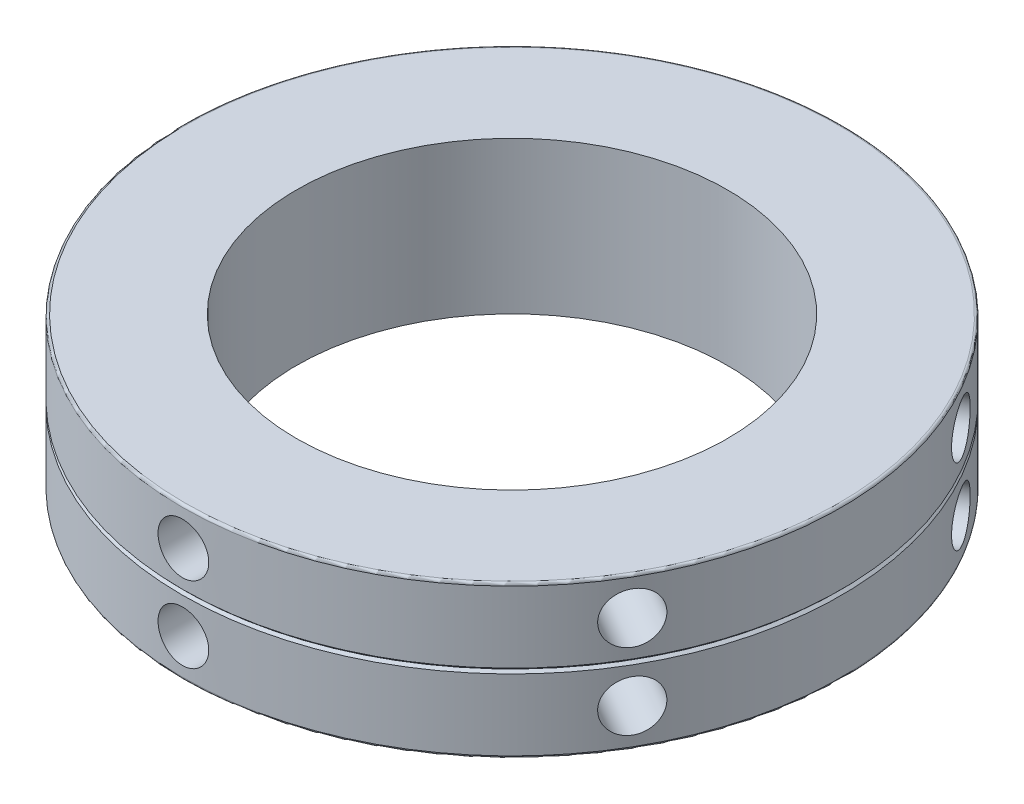
SolidWorks part; units mm, degrees
ref_plane "Front Plane" through (0, 0, 0) normal (0, 0, 1) x (1, 0, 0)
ref_plane "Top Plane" through (0, 0, 0) normal (0, 1, 0) x (1, 0, 0)
ref_plane "Right Plane" through (0, 0, 0) normal (1, 0, 0) x (0, 0, -1)
sketch "Sketch1" plane through (0, 0, 0) normal (0, 1, 0) x (1, 0, 0)
  circle A0 centre (0, 0) radius 26
  circle A1 centre (0, 0) radius 17
  dimension "D1" = 52
  dimension "D2" = 34
extrude "Boss-Extrude1" add sketch "Sketch1" along normal mid plane 12
sketch "Sketch3" plane through (0, 0, 0) normal (0, 0, 1) x (1, 0, 0)
  line L0 (-26, 0) -> (26, 0) construction
  line L1 (-26, 6) -> (-26, -6) construction
  line L2 (26, -6) -> (26, 6) construction
  line L3 (-26, 0.2) -> (-26, -0.2)
  line L4 (-26, -0.2) -> (-25.8, 0)
  line L5 (-26, 0.2) -> (-25.8, 0)
  line L6 (0, -6) -> (0, 6) construction
  line L7 (-26, -6) -> (26, -6) construction
  line L8 (17, 6) -> (-17, 6) construction
  dimension "D1" = 0.2
  dimension "D2" = 0.2
revolve "Cut-Revolve1" cut sketch "Sketch3" angle 360 about L6
fillet "Fillet1" radius 0.2 2 edges at (0, -6, 26) (0, 6, 26)
sketch "Sketch4" plane through (0, 0, 0) normal (0, 0, 1) x (1, 0, 0)
  line L0 (0, -6) -> (0, 6) construction
  line L1 (-25.8, -6) -> (25.8, -6) construction
  line L2 (17, 6) -> (-17, 6) construction
  circle A0 centre (0, 3) radius 2
  dimension "D1" = 4
  dimension "D2" = 3
extrude "Cut-Extrude1" cut sketch "Sketch4" along normal blind 12 from offset 18
pattern_circular "CirPattern1" count 6 over 360 about axis through (0, 6, 0) along (0, -1, 0) of "Cut-Extrude1"
ref_axis "Axis1" through (0, 6, 0) along (0, -1, 0)
pattern_linear "LPattern1" count 2 spacing 6 along (0, -1, 0) of "CirPattern1"
